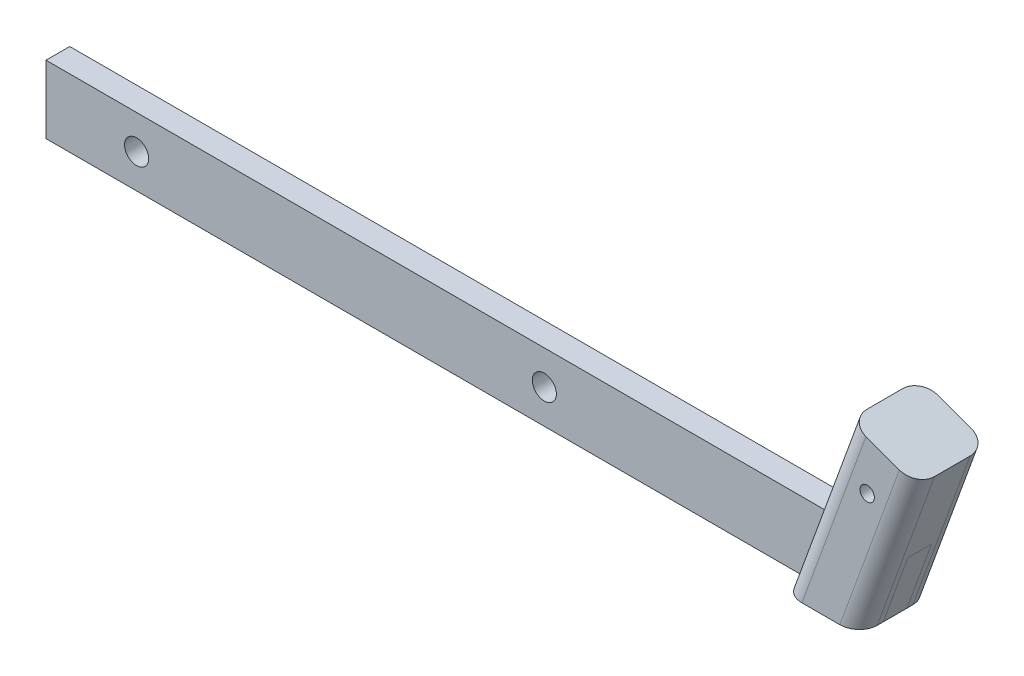
SolidWorks part; units mm, degrees
other "DetailItem2"
other "Weld Folder"
material "AISI 304"
ref_plane "Front Plane" through (0, 0, 0) normal (0, 0, 1) x (1, 0, 0)
ref_plane "Top Plane" through (0, 0, 0) normal (0, 1, 0) x (1, 0, 0)
ref_plane "Right Plane" through (0, 0, 0) normal (1, 0, 0) x (0, 0, -1)
sketch "Sketch8" plane through (0, 0, 0) normal (0, 0, 1) x (1, 0, 0)
  line L0 (0, 0) -> (-223.9659, 0)
  line L1 (0, 0) -> (17.3341, 47.625)
  dimension "D1" = 70
  dimension "D2" = 47.625
  dimension "D3" = 241.3
ref_plane "Plane1" through (17.3341, 47.625, 0) normal (0.342, 0.9397, 0) x (0.9397, -0.342, 0)
sketch "Sketch9" plane through (17.3341, 47.625, 0) normal (0.342, 0.9397, 0) x (0.9397, -0.342, 0)
  line L1 (10.0711, 10.0711) -> (-10.0711, 10.0711)
  line L2 (10.0711, 10.0711) -> (10.0711, -10.0711)
  line L3 (10.0711, -10.0711) -> (-10.0711, -10.0711)
  line L4 (-10.0711, 10.0711) -> (-10.0711, -10.0711)
  line L5 (10.0711, 10.0711) -> (-10.0711, -10.0711) construction
  line L6 (10.0711, -10.0711) -> (-10.0711, 10.0711) construction
  point P0 (0, 0)
  dimension "D1" = 20.1422
extrude "Boss-Extrude2" add sketch "Sketch9" against normal up to surface (47.0159 mm away) up to plane "Top Plane"
ref_plane "Plane2" through (-223.9659, 0, 0) normal (-1, 0, 0) x (0, 0, 1)
sketch "Sketch11" plane through (-223.9659, 0, 0) normal (-1, 0, 0) x (0, 0, 1)
  line L0 (0, 19.05) -> (0, 0) construction
  line L1 (-3.3274, 0) -> (3.3274, 0)
  line L2 (-3.3274, 0) -> (-3.3274, 19.05)
  line L3 (-3.3274, 19.05) -> (3.3274, 19.05)
  line L4 (3.3274, 0) -> (3.3274, 19.05)
  point P10 (0, 0)
  dimension "D1" = 6.6548
  dimension "D2" = 19.05
hole_wizard "#10-32 Tapped Hole1" positions "Sketch12" profile "Sketch13" tap size "#10-32" standard "ANSI Inch" end condition through all
sketch "Sketch12" plane through (0, 0, -10.0711) normal (0, 0, -1) x (-1, 0, 0)
  line L0 (-17.3341, 47.625) -> (-12.9904, 35.6909) construction
  line L1 (-26.7978, 44.1805) -> (-7.8703, 51.0695) construction
  point P0 (-12.9904, 35.6909)
  dimension "D1" = 12.7
cosmetic thread "Hole Thread1" parameters "D2"=4.826
sketch "Sketch13" plane through (12.9904, 35.6909, -10.0711) normal (1, 0, 0) x (0, 1, 0)
  line L0 (0, 0) -> (0, 20.1422)
  line L1 (0, 20.1422) -> (2.0193, 20.1422)
  line L2 (2.0193, 20.1422) -> (2.0193, 0)
  line L5 (2.0193, 0) -> (0, 0)
  line L11 (0, -6.35) -> (0, 107.95) construction
  dimension "Thru Tap Drill Dia." = 4.0386
  dimension "Thru Tap Drill Depth" = 20.1422
extrude "Cut-Extrude2" cut sketch "Sketch11" against normal up to surface (234.6834 mm away) up to face at (18.7576, 22.0902, 0)
fillet "Fillet1" radius 5.08 4 edges at (18.7576, 22.0902, 10.0711) (-1.4235, 25.5348, 10.0711) (-1.4235, 25.5348, -10.0711) (18.7576, 22.0902, -10.0711)
extrude "Boss-Extrude3" add sketch "Sketch11<2>" against normal up to surface (234.6834 mm away) separate body up to face at (16.4709, 15.8076, 0)
sketch "Sketch11<2>" plane through (-223.9659, 0, 0) normal (-1, 0, 0) x (0, 0, 1) same geometry as "Sketch11"
other "Fillet Bead1" [suppressed] parameters "D10"=6.35, "D11"=3.175, "D12"=0, "D13"=3.175, "D14"=0
hole_wizard "1/4 Clearance Hole1" positions "Sketch16" profile "Sketch17" hole size "1/4" standard "ANSI Inch" end condition through all
sketch "Sketch16" plane through (0, 0, -3.3274) normal (0, 0, -1) x (-1, 0, 0)
  line L0 (223.9659, 9.525) -> (0, 9.525) construction
  line L2 (223.9659, 19.05) -> (223.9659, 0) construction
  point P8 (198.5659, 9.525)
  point P10 (84.2659, 9.525)
  point P18 (223.9659, 9.525)
  dimension "D1" = 114.3
  dimension "D2" = 25.4
sketch "Sketch17" plane through (-84.2659, 9.525, -3.3274) normal (1, 0, 0) x (0, 1, 0)
  line L0 (0, 0) -> (0, 13.3985)
  line L1 (0, 13.3985) -> (3.3782, 13.3985)
  line L2 (3.3782, 13.3985) -> (3.3782, 0)
  line L5 (3.3782, 0) -> (0, 0)
  line L11 (0, -6.35) -> (0, 107.95) construction
  dimension "Thru Hole Dia." = 6.7564
  dimension "Thru Hole Depth" = 13.3985
